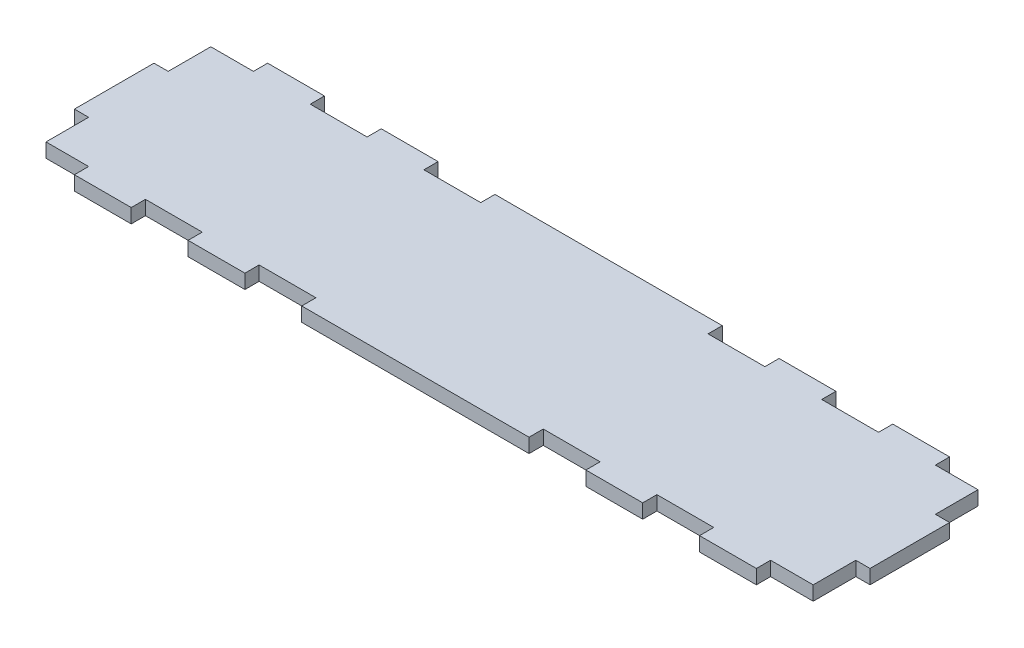
SolidWorks part; units mm, degrees
material "Acrylic (Medium-high impact)"
ref_plane "Front Plane" through (0, 0, 0) normal (0, 0, 1) x (1, 0, 0)
ref_plane "Top Plane" through (0, 0, 0) normal (0, 1, 0) x (1, 0, 0)
ref_plane "Right Plane" through (0, 0, 0) normal (1, 0, 0) x (0, 0, -1)
sketch "Sketch1" plane through (0, 0, 0) normal (0, 1, 0) x (1, 0, 0)
  line L1 (0, 0) -> (171.45, 0)
  line L2 (0, 0) -> (0, 36.83)
  line L3 (0, 36.83) -> (171.45, 36.83)
  line L4 (171.45, 0) -> (171.45, 36.83)
  dimension "D1" = 36.83
  dimension "D2" = 171.45
extrude "Boss-Extrude1" add sketch "Sketch1" along normal blind 3.175
sketch "Sketch2" plane through (0, 3.175, 0) normal (0, 1, 0) x (1, 0, 0)
  line L0 (85.725, 0) -> (85.725, -16.8439) construction
  line L1 (0, 0) -> (171.45, 0) construction
  line L2 (22.225, 0) -> (34.925, 0)
  line L3 (0, 0) -> (-3.175, 0)
  line L4 (0, 0) -> (0, -3.175)
  line L5 (0, -3.175) -> (-3.175, -3.175)
  line L6 (-3.175, 0) -> (-3.175, -3.175)
  line L7 (-3.175, 0) -> (9.525, 0)
  line L8 (-3.175, 0) -> (-3.175, -3.175)
  line L9 (-3.175, -3.175) -> (9.525, -3.175)
  line L10 (9.525, 0) -> (9.525, -3.175)
  line L11 (22.225, 0) -> (22.225, -3.175)
  line L12 (22.225, -3.175) -> (34.925, -3.175)
  line L13 (34.925, 0) -> (34.925, -3.175)
  line L14 (47.625, 0) -> (60.325, 0)
  line L15 (47.625, 0) -> (47.625, -3.175)
  line L16 (47.625, -3.175) -> (60.325, -3.175)
  line L17 (60.325, 0) -> (60.325, -3.175)
  line L18 (-3.175, -3.175) -> (174.625, -3.175)
  line L19 (85.725, -3.175) -> (85.725, 0)
  line L20 (174.625, 0) -> (-3.175, 0)
  line L21 (111.125, 0) -> (111.125, -3.175)
  line L22 (123.825, -3.175) -> (111.125, -3.175)
  line L23 (123.825, 0) -> (123.825, -3.175)
  line L24 (123.825, 0) -> (111.125, 0)
  line L25 (136.525, 0) -> (136.525, -3.175)
  line L26 (149.225, -3.175) -> (136.525, -3.175)
  line L27 (149.225, 0) -> (149.225, -3.175)
  line L28 (161.925, 0) -> (161.925, -3.175)
  line L29 (174.625, -3.175) -> (161.925, -3.175)
  line L30 (174.625, 0) -> (174.625, -3.175)
  line L31 (174.625, 0) -> (161.925, 0)
  line L32 (174.625, 0) -> (174.625, -3.175)
  line L33 (171.45, -3.175) -> (174.625, -3.175)
  line L34 (171.45, 0) -> (171.45, -3.175)
  line L35 (171.45, 0) -> (174.625, 0)
  line L36 (149.225, 0) -> (136.525, 0)
  line M3 (0, 0) -> (171.45, 0)
  dimension "D1" = 3.175
  dimension "D2" = 12.7
  dimension "D3" = 3
extrude "Boss-Extrude2" add sketch "Sketch2" against normal blind 3.175 contours L10 L18 L11 M3 | L13 L18 L15 M3 | L18 L19 L17 M3 | L21 L19 L18 M3 | L25 L23 L18 M3 | L28 L27 L18 M3 region at (15.875, 3.175, 1.5875) region at (41.275, 3.175, 1.5875) region at (73.025, 3.175, 1.5875) region at (98.425, 3.175, 1.5875) region at (130.175, 3.175, 1.5875) region at (155.575, 3.175, 1.5875)
sketch "Sketch3" plane through (0, 3.175, 0) normal (0, 1, 0) x (1, 0, 0)
  line L0 (85.725, -3.175) -> (85.725, 3.175) construction
  line L1 (60.325, -3.175) -> (111.125, -3.175) construction
  line L2 (0, 3.175) -> (171.45, 3.175) construction
  line L3 (0, 36.83) -> (0, 0) construction
  line L4 (171.45, 0) -> (171.45, 36.83) construction
  line L6 (60.325, 0) -> (67.437, 0)
  line L7 (60.325, 0) -> (60.325, 25.654)
  line L8 (60.325, 25.654) -> (67.437, 25.654)
  line L9 (67.437, 0) -> (67.437, 25.654)
  line L10 (111.125, 0) -> (109.855, 0)
  line L11 (111.125, 0) -> (111.125, 29.21)
  line L12 (111.125, 29.21) -> (109.855, 29.21)
  line L13 (109.855, 0) -> (109.855, 29.21)
  line L14 (67.437, 3.175) -> (109.855, 3.175)
  line L15 (67.437, 3.175) -> (67.437, 15.875)
  line L16 (67.437, 15.875) -> (109.855, 15.875)
  line L17 (109.855, 3.175) -> (109.855, 15.875)
  dimension "D1" = 6.35
  dimension "D2" = 7.112
  dimension "D3" = 1.27
  dimension "D4" = 12.7
extrude "Cut-Extrude1" cut sketch "Sketch3" against normal blind 3.175 contours L14 L17 L16 L15
sketch "Sketch5" plane through (0, 3.175, 0) normal (0, 1, 0) x (1, 0, 0)
  line L0 (67.437, 3.175) -> (109.855, 3.175) construction
  line L1 (67.437, 15.875) -> (81.407, 15.875)
  line L2 (67.437, 15.875) -> (67.437, 3.175)
  line L3 (67.437, 3.175) -> (81.407, 3.175)
  line L4 (81.407, 15.875) -> (81.407, 3.175)
  line L5 (67.437, 15.875) -> (109.855, 15.875) construction
  line L6 (109.855, 3.175) -> (98.425, 3.175)
  line L7 (109.855, 3.175) -> (109.855, 15.875)
  line L8 (109.855, 15.875) -> (98.425, 15.875)
  line L9 (98.425, 3.175) -> (98.425, 15.875)
  line L11 (81.407, 15.875) -> (98.425, 15.875)
  line L12 (81.407, 15.875) -> (81.407, 3.175)
  line L13 (81.407, 3.175) -> (98.425, 3.175)
  line L14 (98.425, 15.875) -> (98.425, 3.175)
  line M26 (67.437, 15.875) -> (109.855, 15.875)
  line M28 (109.855, 3.175) -> (67.437, 3.175)
  dimension "D1" = 13.97
  dimension "D2" = 11.43
extrude "Boss-Extrude3" add sketch "Sketch5" against normal blind 3.175 contours L9 L4 M28 M26 region at (89.916, 3.175, -9.525)
sketch "Sketch6" plane through (0, 3.175, 0) normal (0, 1, 0) x (1, 0, 0)
  line L0 (0, 36.83) -> (0, 0) construction
  line L1 (9.525, -3.175) -> (-3.175, -3.175)
  line L2 (9.525, -3.175) -> (9.525, 9.525)
  line L3 (9.525, 9.525) -> (-3.175, 9.525)
  line L4 (-3.175, -3.175) -> (-3.175, 9.525)
  line L5 (161.925, -3.175) -> (174.625, -3.175)
  line L6 (161.925, -3.175) -> (161.925, 9.525)
  line L7 (161.925, 9.525) -> (174.625, 9.525)
  line L8 (174.625, -3.175) -> (174.625, 9.525)
  line L9 (0, 36.83) -> (-3.175, 36.83)
  line L10 (0, 36.83) -> (0, 40.005)
  line L11 (0, 40.005) -> (-3.175, 40.005)
  line L12 (-3.175, 36.83) -> (-3.175, 40.005)
  line L13 (171.45, 36.83) -> (174.625, 36.83)
  line L14 (171.45, 36.83) -> (171.45, 40.005)
  line L15 (171.45, 40.005) -> (174.625, 40.005)
  line L16 (174.625, 36.83) -> (174.625, 40.005)
  line L17 (174.625, 40.005) -> (161.925, 40.005)
  line L18 (174.625, 40.005) -> (174.625, 27.305)
  line L19 (174.625, 27.305) -> (161.925, 27.305)
  line L20 (161.925, 40.005) -> (161.925, 27.305)
  line L21 (-3.175, 40.005) -> (9.525, 40.005)
  line L22 (-3.175, 40.005) -> (-3.175, 27.305)
  line L23 (-3.175, 27.305) -> (9.525, 27.305)
  line L24 (9.525, 40.005) -> (9.525, 27.305)
  line L25 (-3.175, 27.305) -> (0, 27.305)
  line L26 (-3.175, 27.305) -> (-3.175, 9.525)
  line L27 (-3.175, 9.525) -> (0, 9.525)
  line L28 (0, 27.305) -> (0, 9.525)
  line L29 (171.45, 0) -> (171.45, 36.83) construction
  line L30 (174.625, 27.305) -> (171.45, 27.305)
  line L31 (174.625, 27.305) -> (174.625, 9.525)
  line L32 (174.625, 9.525) -> (171.45, 9.525)
  line L33 (171.45, 27.305) -> (171.45, 9.525)
  line M5 (0, 36.83) -> (0, 0)
  line M27 (171.45, 0) -> (171.45, 36.83)
  dimension "D1" = 12.7
  dimension "D2" = 12.7
  dimension "D3" = 12.7
  dimension "D4" = 3.175
  dimension "D5" = 3.175
  dimension "D6" = 12.7
  dimension "D7" = 12.7
extrude "Boss-Extrude4" add sketch "Sketch6" against normal blind 3.175 contours L31 L19 L7 M27 | L23 L26 L3 M5 region at (-1.5875, 3.175, -18.415) region at (173.0375, 3.175, -18.415)
ref_plane "Plane2" through (0, 0, -18.415) normal (0, 0, -1) x (-1, 0, 0)
mirror "Mirror1" about plane through (0, 0, -18.415) normal (0, 0, -1) of "Boss-Extrude2"
sketch "Sketch7" plane through (0, 3.175, 0) normal (0, 1, 0) x (1, 0, 0)
  line L1 (56.1342, 26.5004) -> (115.4825, 26.5004)
  line L2 (56.1342, 26.5004) -> (56.1342, 1.3273)
  line L3 (56.1342, 1.3273) -> (115.4825, 1.3273)
  line L4 (115.4825, 26.5004) -> (115.4825, 1.3273)
extrude "Boss-Extrude5" add sketch "Sketch7" against normal blind 3.175
